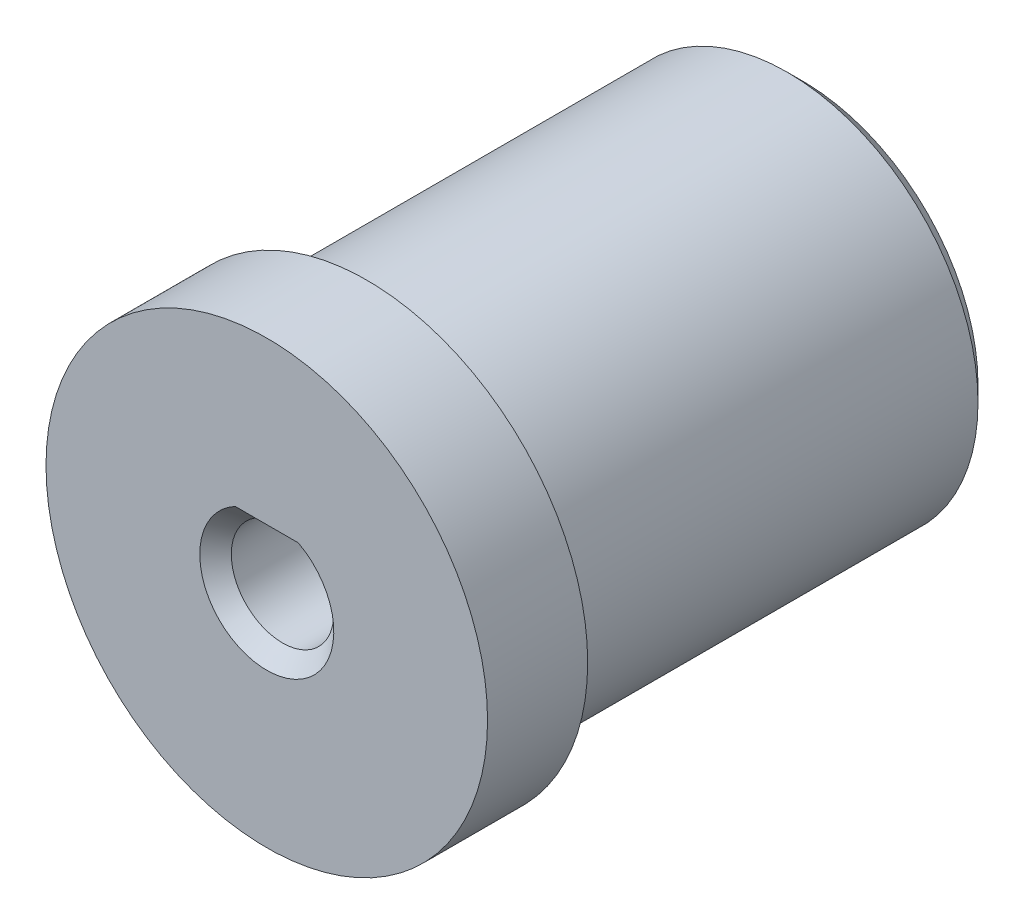
SolidWorks part; units mm, degrees
ref_plane "Front Plane" through (0, 0, 0) normal (0, 0, 1) x (1, 0, 0)
ref_plane "Top Plane" through (0, 0, 0) normal (0, 1, 0) x (1, 0, 0)
ref_plane "Right Plane" through (0, 0, 0) normal (1, 0, 0) x (0, 0, -1)
sketch "Sketch2" plane through (0, 0, 0) normal (0, 0, 1) x (1, 0, 0)
  line L0 (-1.7321, 2.75) -> (1.7321, 2.75)
  circle A0 centre (0, 0) radius 3.25
  circle A1 centre (0, 0) radius 12.1
  point P5 (0, 3.25)
  dimension "D1" = 6.5
  dimension "D3" = 24.2
  dimension "D2" = 0.5
extrude "Boss-Extrude1" add sketch "Sketch2" along normal blind 34 contours A1 A0 | L0 A0 region at (0, 2.9514, 0) region at (-11.7578, 0, 0)
sketch "Sketch3" plane through (0, 0, 34) normal (0, 0, 1) x (1, 0, 0)
  circle A0 centre (0, 0) radius 14
  arc M1 (1.7321, 2.75) -> (-1.7321, 2.75) centre (0, 0) cw
  line M2 (-1.7321, 2.75) -> (1.7321, 2.75)
  circle M3 centre (0, 0) radius 12.1
  dimension "D1" = 28
extrude "Boss-Extrude2" add sketch "Sketch3" against normal blind 6.35 contours M3 M2 M1 | A0 M3 region at (-13.604, 0, 34) region at (-11.7578, 0, 34)
chamfer "Chamfer1" distance 1 angle 45 5 edges at (0, 2.75, 0) (0, -3.25, 0) (12.1, 0, 0) (0, -3.25, 34) (0, 2.75, 34)
